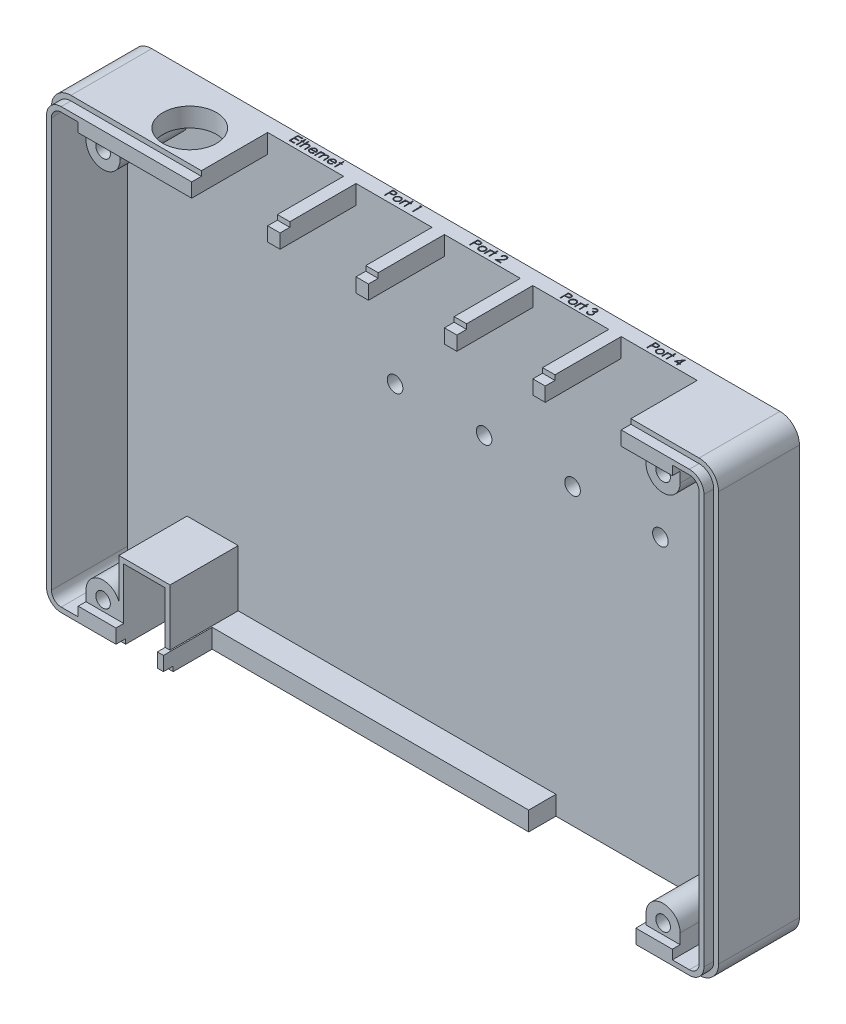
SolidWorks part; units mm, degrees
ref_plane "Front Plane" through (0, 0, 0) normal (0, 0, 1) x (1, 0, 0)
ref_plane "Top Plane" through (0, 0, 0) normal (0, 1, 0) x (1, 0, 0)
ref_plane "Right Plane" through (0, 0, 0) normal (1, 0, 0) x (0, 0, -1)
sketch "Sketch1" plane through (0, 0, 0) normal (0, 0, 1) x (1, 0, 0)
  line L1 (0, 0) -> (137, 0)
  line L2 (0, 0) -> (0, 92)
  line L3 (0, 92) -> (137, 92)
  line L4 (137, 0) -> (137, 92)
  dimension "D1" = 137
  dimension "D2" = 92
extrude "Boss-Extrude1" add sketch "Sketch1" along normal blind 2 and the other way blind 1
sketch "Sketch2" plane through (0, 0, 2) normal (0, 0, 1) x (1, 0, 0)
  line L1 (0, 92) -> (137, 92)
  line L2 (0, 92) -> (0, 0)
  line L3 (0, 0) -> (137, 0)
  line L4 (137, 92) -> (137, 0)
  line L5 (2, 2) -> (135, 2)
  line L6 (2, 2) -> (2, 90)
  line L7 (2, 90) -> (135, 90)
  line L8 (135, 2) -> (135, 90)
  dimension "D1" = 2
  dimension "D2" = 2
  dimension "D3" = 2
  dimension "D4" = 2
extrude "Boss-Extrude2" add sketch "Sketch2" along normal blind 15.6
sketch "Sketch3" plane through (0, 0, 17.6) normal (0, 0, 1) x (1, 0, 0)
  line L1 (0, 0) -> (137, 0)
  line L2 (0, 0) -> (0, 92)
  line L3 (0, 92) -> (137, 92)
  line L4 (137, 0) -> (137, 92)
  line L5 (1, 1) -> (136, 1)
  line L6 (1, 1) -> (1, 91)
  line L7 (1, 91) -> (136, 91)
  line L8 (136, 1) -> (136, 91)
  dimension "D1" = 1
  dimension "D2" = 1
  dimension "D3" = 1
  dimension "D4" = 1
extrude "Boss-Extrude3" add sketch "Sketch3" along normal blind 2
sketch "Sketch4" plane through (0, 0, 2) normal (0, 0, 1) x (1, 0, 0)
  line L0 (0, 0) -> (137, 0) construction
  line L1 (0, 92) -> (0, 0) construction
  line L2 (2, 2) -> (135, 2) construction
  line L4 (7.5, 6) -> (7.5, 2)
  line L5 (7.5, 2) -> (14.5, 2)
  line L6 (14.5, 6) -> (14.5, 2)
  line L7 (137, 0) -> (137, 92) construction
  line L8 (137, 92) -> (0, 92) construction
  line L9 (2, 2) -> (135, 2) construction
  line L11 (122.5, 6) -> (122.5, 2)
  line L12 (122.5, 2) -> (129.5, 2)
  line L13 (129.5, 6) -> (129.5, 2)
  line L14 (135, 90) -> (2, 90) construction
  line L16 (129.5, 86) -> (129.5, 90)
  line L17 (129.5, 90) -> (122.5, 90)
  line L18 (122.5, 86) -> (122.5, 90)
  line L19 (135, 90) -> (2, 90) construction
  line L21 (14.5, 86) -> (14.5, 90)
  line L22 (14.5, 90) -> (7.5, 90)
  line L23 (7.5, 86) -> (7.5, 90)
  arc A0 (14.5, 6) -> (7.5, 6) centre (11, 6) ccw
  circle A1 centre (11, 6) radius 1.5
  arc A2 (7.5, 86) -> (14.5, 86) centre (11, 86) ccw
  circle A3 centre (11, 86) radius 1.5
  arc A4 (122.5, 86) -> (129.5, 86) centre (126, 86) ccw
  circle A5 centre (126, 86) radius 1.5
  arc A6 (129.5, 6) -> (122.5, 6) centre (126, 6) ccw
  circle A7 centre (126, 6) radius 1.5
  dimension "D1" = 3
  dimension "D2" = 7
  dimension "D3" = 3
  dimension "D4" = 7
  dimension "D5" = 3
  dimension "D6" = 7
  dimension "D7" = 3
  dimension "D8" = 7
  dimension "D11" = 6
  dimension "D9" = 6
  dimension "D10" = 11
  dimension "D12" = 11
  dimension "D13" = 11
  dimension "D14" = 6
  dimension "D15" = 11
  dimension "D16" = 6
extrude "Boss-Extrude4" add sketch "Sketch4" along normal blind 15.6
sketch "Sketch8" plane through (0, 0, 2) normal (0, 0, 1) x (1, 0, 0)
  line L0 (122.5, 6) -> (122.5, 2) construction
  line L1 (14.5, 2) -> (122.5, 2)
  line L2 (14.5, 2) -> (14.5, 3.9)
  line L3 (14.5, 3.9) -> (122.5, 3.9)
  line L4 (122.5, 2) -> (122.5, 3.9)
  dimension "D1" = 1.9
extrude "Boss-Extrude6" add sketch "Sketch8" along normal blind 15.6
sketch "Sketch11" plane through (0, 0, 2) normal (0, 0, 1) x (1, 0, 0)
  line L0 (122.5, 90) -> (122.5, 86) construction
  line L1 (14.5, 90) -> (122.5, 90)
  line L2 (14.5, 90) -> (14.5, 88.1)
  line L3 (14.5, 88.1) -> (122.5, 88.1)
  line L4 (122.5, 90) -> (122.5, 88.1)
  dimension "D1" = 1.9
extrude "Boss-Extrude7" add sketch "Sketch11" along normal blind 15.6
sketch "Sketch14" plane through (0, 0, 19.6) normal (0, 0, 1) x (1, 0, 0)
  line L1 (0, 92) -> (137, 92)
  line L2 (0, 92) -> (0, 0)
  line L3 (0, 0) -> (137, 0)
  line L4 (137, 92) -> (137, 0)
  line L5 (1, 1) -> (136, 1)
  line L6 (1, 1) -> (1, 91)
  line L7 (1, 91) -> (136, 91)
  line L8 (136, 1) -> (136, 91)
extrude "Cut-Extrude5" cut sketch "Sketch14" against normal blind 4
fillet "Fillet1" radius 2 4 edges at (2, 2, 9.8) (135, 2, 9.8) (135, 90, 9.8) (2, 90, 9.8)
fillet "Fillet3" radius 3 4 edges at (1, 1, 16.6) (136, 1, 16.6) (136, 91, 16.6) (1, 91, 16.6)
fillet "Fillet4" radius 4 4 edges at (0, 92, 7.3) (137, 92, 7.3) (137, 0, 7.3) (0, 0, 7.3)
sketch "Sketch15" plane through (0, 92, 0) normal (0, 1, 0) x (1, 0, 0)
  line L0 (133, -15.6) -> (4, -15.6) construction
  line L1 (0, -15.6) -> (0, 1) construction
  circle A0 centre (22, -9.2) radius 5.5
  dimension "D1" = 11
  dimension "D2" = 6.4
  dimension "D3" = 22
extrude "Cut-Extrude6" cut sketch "Sketch15" against normal blind 4
sketch "Sketch16" plane through (0, 92, 0) normal (0, 1, 0) x (1, 0, 0)
  line L0 (0, -15.6) -> (0, 1) construction
  line L1 (30.8, -17.6) -> (46.4, -17.6)
  line L2 (30.8, -17.6) -> (30.8, -2)
  line L3 (30.8, -2) -> (46.4, -2)
  line L4 (46.4, -17.6) -> (46.4, -2)
  line L5 (133, -17.6) -> (4, -17.6) construction
  dimension "D1" = 30.8
  dimension "D2" = 0
  dimension "D3" = 15.6
  dimension "D4" = 15.6
extrude "Cut-Extrude7" cut sketch "Sketch16" against normal blind 4
sketch "Sketch17" plane through (0, 92, 0) normal (0, 1, 0) x (1, 0, 0)
  line L19 (133, -17.6) -> (46.4, -17.6) construction
  line L20 (48.95, -17.6) -> (64.55, -17.6)
  line L21 (48.95, -17.6) -> (48.95, -2)
  line L22 (48.95, -2) -> (64.55, -2)
  line L23 (64.55, -17.6) -> (64.55, -2)
  line L24 (67.1, -17.6) -> (82.7, -17.6)
  line L25 (67.1, -17.6) -> (67.1, -2)
  line L26 (67.1, -2) -> (82.7, -2)
  line L27 (82.7, -17.6) -> (82.7, -2)
  line L28 (85.25, -17.6) -> (100.85, -17.6)
  line L29 (85.25, -17.6) -> (85.25, -2)
  line L30 (85.25, -2) -> (100.85, -2)
  line L31 (100.85, -17.6) -> (100.85, -2)
  line L32 (103.4, -17.6) -> (119, -17.6)
  line L33 (103.4, -17.6) -> (103.4, -2)
  line L34 (103.4, -2) -> (119, -2)
  line L35 (119, -17.6) -> (119, -2)
  line L36 (0, -15.6) -> (0, 1) construction
  dimension "D1" = 15.6
  dimension "D2" = 15.6
  dimension "D3" = 15.6
  dimension "D4" = 15.6
  dimension "D5" = 15.6
  dimension "D6" = 15.6
  dimension "D7" = 15.6
  dimension "D8" = 15.6
  dimension "D9" = 0
  dimension "D10" = 0
  dimension "D11" = 0
  dimension "D12" = 48.95
  dimension "D13" = 67.1
  dimension "D14" = 85.25
  dimension "D15" = 103.4
  dimension "D16" = 0
extrude "Cut-Extrude8" cut sketch "Sketch17" against normal blind 4
sketch "Sketch19" plane through (0, 0, -1) normal (0, 0, -1) x (-1, 0, 0)
  circle A0 centre (-56.9642, 60.3523) radius 1.6
  circle A1 centre (-75.2522, 60.3523) radius 1.6
  circle A2 centre (-93.4132, 60.3523) radius 1.6
  circle A3 centre (-111.4472, 60.3523) radius 1.6
  dimension "D1" = 3.2
  dimension "D2" = 3.2
  dimension "D3" = 3.2
  dimension "D4" = 3.2
extrude "Cut-Extrude9" cut sketch "Sketch19" against normal blind 4
sketch "Sketch20" plane through (0, 0, 0) normal (0, -1, 0) x (1, 0, 0)
  line L0 (4, 17.6) -> (133, 17.6) construction
  line L1 (122, 17.6) -> (90, 17.6)
  line L2 (122, 17.6) -> (122, 2)
  line L3 (122, 2) -> (90, 2)
  line L4 (90, 17.6) -> (90, 2)
  line L5 (137, 15.6) -> (137, -1) construction
  dimension "D1" = 32
  dimension "D2" = 15.6
  dimension "D3" = 0
  dimension "D4" = 15
extrude "Cut-Extrude10" cut sketch "Sketch20" against normal blind 4
sketch "Sketch21" plane through (0, 0, 0) normal (0, -1, 0) x (1, 0, 0)
  line L1 (90, 17.6) -> (25, 17.6)
  line L2 (90, 17.6) -> (90, 7.6)
  line L3 (90, 7.6) -> (25, 7.6)
  line L4 (25, 17.6) -> (25, 7.6)
  dimension "D1" = 65
  dimension "D2" = 10
extrude "Cut-Extrude11" cut sketch "Sketch21" against normal blind 4
sketch "Sketch22" plane through (0, 0, 17.6) normal (0, 0, 1) x (1, 0, 0)
  line L1 (122.5, 88.1) -> (130.7778, 88.1)
  line L2 (122.5, 88.1) -> (122.5, 81.9328)
  line L3 (122.5, 81.9328) -> (130.7778, 81.9328)
  line L4 (130.7778, 88.1) -> (130.7778, 81.9328)
extrude "Cut-Extrude12" cut sketch "Sketch22" against normal blind 1.6
sketch "Sketch23" plane through (0, 0, 17.6) normal (0, 0, 1) x (1, 0, 0)
  line L1 (122.5, 3.9) -> (130.3517, 3.9)
  line L2 (122.5, 3.9) -> (122.5, 10.7356)
  line L3 (122.5, 10.7356) -> (130.3517, 10.7356)
  line L4 (130.3517, 3.9) -> (130.3517, 10.7356)
extrude "Cut-Extrude13" cut sketch "Sketch23" against normal blind 1.6
sketch "Sketch24" plane through (0, 0, 17.6) normal (0, 0, 1) x (1, 0, 0)
  line L1 (14.5, 3.9) -> (6.9446, 3.9)
  line L2 (14.5, 3.9) -> (14.5, 10.0585)
  line L3 (14.5, 10.0585) -> (6.9446, 10.0585)
  line L4 (6.9446, 3.9) -> (6.9446, 10.0585)
extrude "Cut-Extrude14" cut sketch "Sketch24" against normal blind 1.6
sketch "Sketch25" plane through (0, 0, 17.6) normal (0, 0, 1) x (1, 0, 0)
  line L1 (14.5, 88.1) -> (6.2877, 88.1)
  line L2 (14.5, 88.1) -> (14.5, 80.2964)
  line L3 (14.5, 80.2964) -> (6.2877, 80.2964)
  line L4 (6.2877, 88.1) -> (6.2877, 80.2964)
extrude "Cut-Extrude15" cut sketch "Sketch25" against normal blind 1.6
sketch "Sketch26" plane through (0, 0, -1) normal (0, 0, -1) x (-1, 0, 0)
  line L0 (-4, 0) -> (-133, 0) construction
  line L1 (0, 88) -> (0, 4) construction
  line L2 (-15.25, 0) -> (-23.75, 0)
  line L3 (-15.25, 0) -> (-15.25, 14.5)
  line L4 (-15.25, 14.5) -> (-23.75, 14.5)
  line L5 (-23.75, 0) -> (-23.75, 14.5)
  dimension "D1" = 8.5
  dimension "D2" = 14.5
  dimension "D3" = 15.25
extrude "Cut-Extrude16" cut sketch "Sketch26" against normal blind 23.6
sketch "Sketch29" plane through (0, 0, 2) normal (0, 0, 1) x (1, 0, 0)
  line L0 (25, 3.9) -> (23.75, 3.9) construction
  line L1 (15.25, 3.9) -> (14.25, 3.9)
  line L2 (24.75, 3.9) -> (23.75, 3.9)
  line L3 (24.75, 3.9) -> (24.75, 15.5)
  line L4 (24.75, 15.5) -> (14.25, 15.5)
  line L5 (14.25, 3.9) -> (14.25, 15.5)
  line L7 (23.75, 3.9) -> (23.75, 14.5)
  line L8 (23.75, 14.5) -> (15.25, 14.5)
  line L9 (15.25, 3.9) -> (15.25, 14.5)
  dimension "D1" = 1
  dimension "D2" = 1
  dimension "D3" = 1
extrude "Boss-Extrude8" add sketch "Sketch29" along normal blind 14
sketch "Sketch30" plane through (0, 92, 0) normal (0, 1, 0) x (1, 0, 0)
  text T0 "Ethernet" font "Century Gothic" height 1.8
extrude "Cut-Extrude17" cut sketch "Sketch30" against normal blind 0.5
sketch "Sketch31" plane through (0, 92, 0) normal (0, 1, 0) x (1, 0, 0)
  text T0 "Port 1" font "Century Gothic" height 1.8
extrude "Cut-Extrude18" cut sketch "Sketch31" against normal blind 0.5
sketch "Sketch32" plane through (0, 92, 0) normal (0, 1, 0) x (1, 0, 0)
  text T0 "Port 2" font "Century Gothic" height 1.8
extrude "Cut-Extrude19" cut sketch "Sketch32" against normal blind 0.5
sketch "Sketch33" plane through (0, 92, 0) normal (0, 1, 0) x (1, 0, 0)
  text T0 "Port 3" font "Century Gothic" height 1.8
extrude "Cut-Extrude20" cut sketch "Sketch33" against normal blind 0.5
sketch "Sketch34" plane through (0, 92, 0) normal (0, 1, 0) x (1, 0, 0)
  text T0 "Port 4" font "Century Gothic" height 1.8
extrude "Cut-Extrude21" cut sketch "Sketch34" against normal blind 0.5
